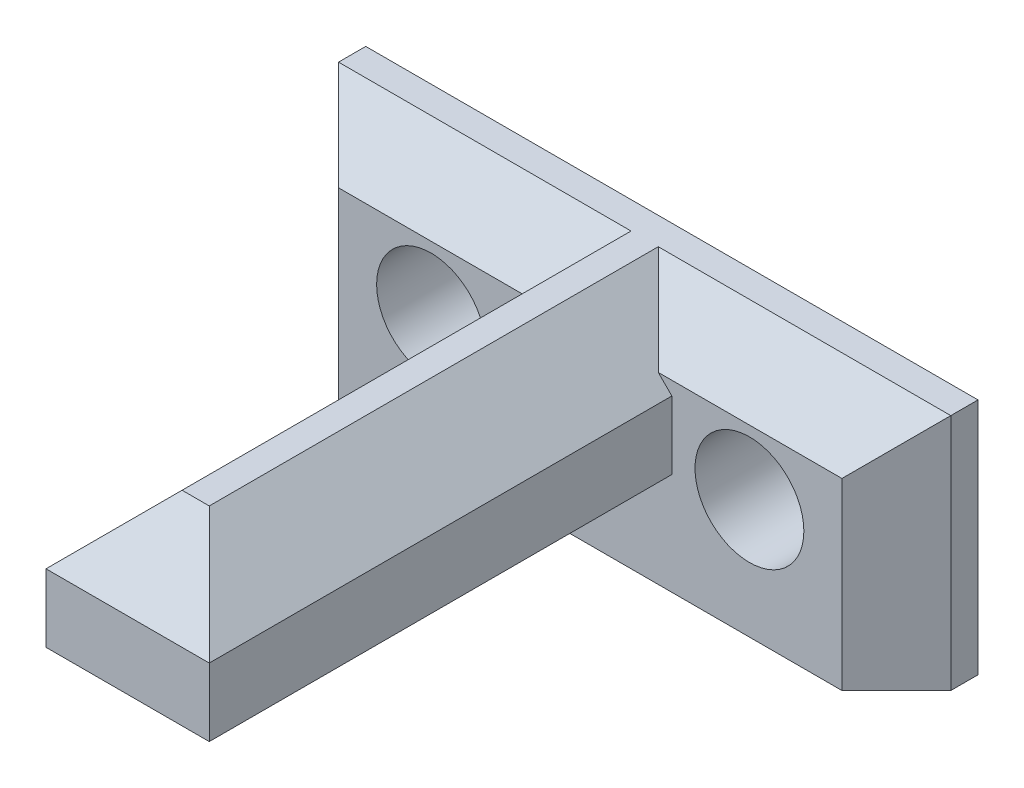
SolidWorks part; units mm, degrees
ref_plane "前视基准面" through (0, 0, 0) normal (0, 0, 1) x (1, 0, 0)
ref_plane "上视基准面" through (0, 0, 0) normal (0, 1, 0) x (1, 0, 0)
ref_plane "右视基准面" through (0, 0, 0) normal (1, 0, 0) x (0, 0, -1)
other "Configuration Table"
sketch "Sketch1" plane through (0, 0, 0) normal (0, 0, 1) x (1, 0, 0)
  line L0 (0, 0) -> (5.85, 0) construction
  line L1 (-11.25, -4.375) -> (11.25, -4.375)
  line L2 (-11.25, -4.375) -> (-11.25, 4.375)
  line L3 (-11.25, 4.375) -> (11.25, 4.375)
  line L4 (11.25, -4.375) -> (11.25, 4.375)
  line L5 (-11.25, -4.375) -> (11.25, 4.375) construction
  line L6 (-11.25, 4.375) -> (11.25, -4.375) construction
  line L7 (0, 0) -> (0, 4.375) construction
  circle A0 centre (5.85, 0) radius 2
  circle A1 centre (-5.85, 0) radius 2
  point P0 (0, 0)
  dimension "D3" = 4
  dimension "D1" = 22.5
  dimension "D2" = 8.75
  dimension "D4" = 5.85
extrude "Boss-Extrude1" add sketch "Sketch1" along normal blind 3
sketch "Sketch2" plane through (0, 4.375, 0) normal (0, 1, 0) x (1, 0, 0)
  line L0 (-3, 0) -> (3, 0)
  line L1 (11.25, 0) -> (-11.25, 0) construction
  line L6 (3, 0) -> (3, -20)
  line L7 (3, -20) -> (-3, -20)
  line L8 (0, -20) -> (0, 0)
  line L9 (-3, 0) -> (-3, -20)
  line M6 (-11.25, -3) -> (11.25, -3)
  dimension "D1" = 6
  dimension "D2" = 20
extrude "Boss-Extrude2" add sketch "Sketch2" against normal blind 5 contours L9 L7 L8 M6 | L8 L7 L6 M6 region at (-1.5, 4.375, 11.5) region at (1.5, 4.375, 11.5)
chamfer "Chamfer1" distance 2 angle 45 4 edges at (11.25, 0, 3) (7.125, 4.375, 3) (-11.25, 0, 3) (-7.125, 4.375, 3)
chamfer "Chamfer2" distance 2.5 angle 45 3 edges at (3, 4.375, 10.5) (0, 4.375, 20) (-3, 4.375, 10.5)
